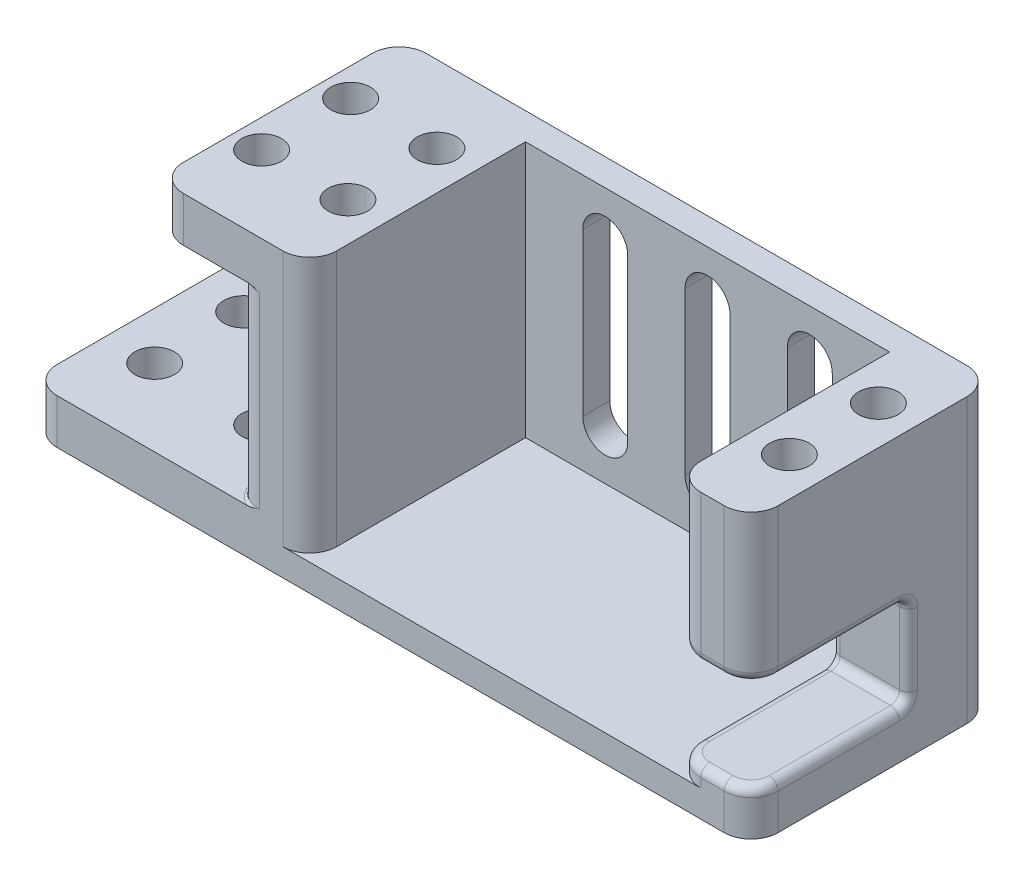
SolidWorks part; units mm, degrees
ref_plane "Front Plane" through (0, 0, 0) normal (0, 0, 1) x (1, 0, 0)
ref_plane "Top Plane" through (0, 0, 0) normal (0, 1, 0) x (1, 0, 0)
ref_plane "Right Plane" through (0, 0, 0) normal (1, 0, 0) x (0, 0, -1)
sketch "Sketch1" plane through (0, 0, 0) normal (0, 1, 0) x (1, 0, 0)
  line L0 (0, 13.5) -> (0, -13.5)
  line L1 (0, -13.5) -> (8.6, -13.5)
  line L3 (0, 13.5) -> (8.6, 13.5)
  line L4 (8.6, -13.5) -> (8.6, 13.5)
  line L5 (0, 0) -> (8.6, 0) construction
  point P0 (0, 0)
  dimension "D1" = 8.6
  dimension "D2" = 27
extrude "Boss-Extrude1" add sketch "Sketch1" along normal blind 31.5
sketch "Sketch2" plane through (8.6, 0, 0) normal (1, 0, 0) x (0, 0, -1)
  line L0 (-13.5, 0) -> (13.5, 0)
  line L1 (-13.5, 0) -> (-13.5, 3)
  line L2 (13.5, 0) -> (13.5, 3)
  line L3 (-13.5, 3) -> (13.5, 3)
  line L4 (-13.5, 31.5) -> (-13.5, 0) construction
  line L5 (13.5, 31.5) -> (13.5, 0) construction
  dimension "D1" = 3
extrude "Boss-Extrude2" add sketch "Sketch2" along normal blind 40.5
sketch "Sketch3" plane through (8.6, 0, 0) normal (1, 0, 0) x (0, 0, -1)
  line L0 (10.5, 31.5) -> (10.5, 3)
  line L1 (10.5, 31.5) -> (13.5, 31.5)
  line L2 (10.5, 3) -> (13.5, 3)
  line L3 (13.5, 31.5) -> (13.5, 3)
  line L4 (0, 31.5) -> (0, 3) construction
  line L5 (-13.5, 31.5) -> (13.5, 31.5) construction
  line L6 (13.5, 3) -> (-13.5, 3) construction
  dimension "D1" = 3
extrude "Boss-Extrude3" add sketch "Sketch3" along normal blind 40.5
sketch "Sketch4" plane through (0, 31.5, 0) normal (0, 1, 0) x (1, 0, 0)
  line L0 (49.1, 13.5) -> (49.1, -13.5)
  line L1 (49.1, 13.5) -> (57.7, 13.5)
  line L2 (49.1, -13.5) -> (57.7, -13.5)
  line L3 (57.7, 13.5) -> (57.7, -13.5)
  line L4 (49.1, 13.5) -> (49.1, 10.5) construction
  line L5 (0, -13.5) -> (8.6, -13.5) construction
  dimension "D1" = 8.6
extrude "Boss-Extrude4" add sketch "Sketch4" against normal blind 31.5
sketch "Sketch15" plane through (0, 0, -10.5) normal (0, 0, 1) x (1, 0, 0)
  line L0 (28.85, 31.5) -> (28.85, 3) construction
  line L1 (49.1, 31.5) -> (8.6, 31.5) construction
  line L2 (49.1, 3) -> (8.6, 3) construction
  line L5 (31.35, 8.25) -> (31.35, 26.25)
  line L7 (26.35, 8.25) -> (26.35, 26.25)
  line L8 (28.85, 17.25) -> (26.35, 26.25) construction
  line L9 (31.35, 26.25) -> (28.85, 17.25) construction
  line L10 (8.6, 17.25) -> (49.1, 17.25) construction
  line L11 (8.6, 31.5) -> (8.6, 3) construction
  line L12 (49.1, 3) -> (49.1, 31.5) construction
  line L13 (42.725, 8.25) -> (42.725, 26.25)
  line L14 (28.85, 17.25) -> (26.35, 8.25) construction
  line L15 (31.35, 8.25) -> (28.85, 17.25) construction
  line L16 (37.725, 8.25) -> (37.725, 26.25)
  line L17 (40.225, 28.75) -> (40.225, 5.75) construction
  line L18 (19.975, 8.25) -> (19.975, 26.25)
  line L19 (14.975, 8.25) -> (14.975, 26.25)
  arc A0 (31.35, 26.25) -> (26.35, 26.25) centre (28.85, 26.25) ccw
  arc A1 (31.35, 8.25) -> (26.35, 8.25) centre (28.85, 8.25) cw
  arc A2 (42.725, 26.25) -> (37.725, 26.25) centre (40.225, 26.25) ccw
  arc A3 (42.725, 8.25) -> (37.725, 8.25) centre (40.225, 8.25) cw
  arc A4 (14.975, 8.25) -> (19.975, 8.25) centre (17.475, 8.25) ccw
  arc A5 (14.975, 26.25) -> (19.975, 26.25) centre (17.475, 26.25) cw
  point P6 (28.85, 17.25)
  dimension "D1" = 18
  dimension "D2" = 5
  dimension "D4" = 11.375
  dimension "D3" = 2
extrude "Cut-Extrude8" cut sketch "Sketch15" against normal blind 10
fillet "Fillet1" radius 3 4 edges at (57.7, 15.75, 13.5) (57.7, 15.75, -13.5) (8.6, 17.25, 13.5) (49.1, 17.25, 13.5)
sketch "Sketch5" plane through (0, 31.5, 0) normal (0, 1, 0) x (1, 0, 0)
  line L0 (0, 0) -> (8.6, 0) construction
  line L1 (8.6, 10.5) -> (8.6, -10.5) construction
  line L2 (0, 13.5) -> (0, -13.5) construction
  line L3 (8.6, 10.5) -> (8.6, -10.5) construction
  line L7 (49.1, 10.5) -> (49.1, -10.5) construction
  circle A0 centre (53.4, 4.95) radius 2.2
  circle A1 centre (53.4, -4.95) radius 2.2
  circle A2 centre (4.3, 4.95) radius 2.2
  circle A3 centre (4.3, -4.95) radius 2.2
  dimension "D1" = 4.4
  dimension "D3" = 4.4
  dimension "D6" = 4.3
  dimension "D7" = 4.3
  dimension "D2" = 9.9
  dimension "D4" = 9.9
  dimension "D5" = 4.95
extrude "Cut-Extrude1" cut sketch "Sketch5" against normal blind 5
sketch "Sketch6" plane through (49.1, 0, 0) normal (-1, 0, 0) x (0, 0, 1)
  line L0 (13.5, 15) -> (13.5, 5)
  line L1 (13.5, 15) -> (-4, 15)
  line L2 (13.5, 5) -> (-4, 5)
  line L3 (-4, 15) -> (-4, 5)
  line L4 (13.5, 3) -> (13.5, 31.5) construction
  line L5 (0, 3) -> (0, 31.5) construction
  line L6 (-10.5, 3) -> (10.5, 3) construction
  line L7 (-10.5, 31.5) -> (10.5, 31.5) construction
  line L8 (-10.5, 3) -> (10.5, 3) construction
  dimension "D1" = 4
  dimension "D2" = 10
  dimension "D3" = 2
extrude "Cut-Extrude2" cut sketch "Sketch6" against normal blind 10
fillet "Fillet3" radius 1 14 edges at (56.8213, 5, 12.6213) (56.8213, 15, 12.6213) (57.7, 10, -4) (49.1, 5, 3.25) (49.1, 15, 3.25) (49.1, 10, -4) (49.9787, 15, 12.6213) (57.7, 15, 3.25) (53.4, 15, 13.5) (49.9787, 5, 12.6213) (57.7, 5, 3.25) (53.4, 15, -4) (53.4, 5, 13.5) (53.4, 5, -4)
sketch "Sketch9" plane through (0, 0, 0) normal (-1, 0, 0) x (0, 0, 1)
  line L4 (-13.5, 31.5) -> (-13.5, 0) construction
  line L5 (13.5, 15.75) -> (-13.5, 15.75) construction
  line L6 (13.5, 31.5) -> (13.5, 0) construction
  line L7 (-13.5, 15.75) -> (13.5, 15.75) construction
  line L8 (-13.5, 31.5) -> (13.5, 31.5)
  line L9 (-13.5, 31.5) -> (-13.5, 26.5)
  line L10 (13.5, 31.5) -> (13.5, 26.5)
  line L11 (-13.5, 26.5) -> (13.5, 26.5)
  line L12 (13.5, 0) -> (13.5, 5)
  line L13 (-13.5, 5) -> (13.5, 5)
  line L14 (-13.5, 0) -> (-13.5, 5)
  line L15 (-13.5, 0) -> (13.5, 0)
  line L16 (-13.5, 31.5) -> (13.5, 31.5) construction
  dimension "D1" = 5
  dimension "D2" = 0
extrude "Boss-Extrude5" add sketch "Sketch9" along normal blind 22.5
sketch "Sketch10" plane through (0, 31.5, 0) normal (0, 1, 0) x (1, 0, 0)
  line L0 (-22.5, 0) -> (0, 0) construction
  line L1 (-22.5, -13.5) -> (-22.5, 13.5) construction
  line L2 (0, 13.5) -> (0, -13.5) construction
  circle A0 centre (-5.3, 4.95) radius 2.2
  circle A1 centre (-5.3, -4.95) radius 2.2
  circle A2 centre (-17.2, -4.95) radius 2.2
  circle A3 centre (-17.2, 4.95) radius 2.2
  dimension "D1" = 4.4
  dimension "D3" = 4.95
  dimension "D4" = 5.3
  dimension "D5" = 11.9
  dimension "D2" = 9.9
extrude "Cut-Extrude5" cut sketch "Sketch10" against normal blind 100
fillet "Fillet4" radius 3 4 edges at (0, 15.75, 13.5) (0, 15.75, -13.5) (-22.5, 2.5, 13.5) (-22.5, 2.5, -13.5)
fillet "Fillet5" radius 0.3 6 edges at (0, 5, 0) (0, 26.5, 0) (0.8787, 5, -12.6213) (0.8787, 26.5, -12.6213) (0.8787, 5, 12.6213) (0.8787, 26.5, 12.6213)
sketch "Sketch12" plane through (0, 31.5, 0) normal (0, 1, 0) x (1, 0, 0)
  line L0 (-22.5, -13.5) -> (5.6, -13.5) construction
  line L1 (-22.5, 13.5) -> (-8.45, 13.5)
  line L2 (-22.5, 13.5) -> (-22.5, -13.5)
  line L3 (-22.5, -13.5) -> (-8.45, -13.5)
  line L4 (-8.45, 13.5) -> (-8.45, -13.5)
extrude "Cut-Extrude6" cut sketch "Sketch12" against normal blind 10
fillet "Fillet6" radius 3 2 edges at (-8.45, 29, -13.5) (-8.45, 29, 13.5)
